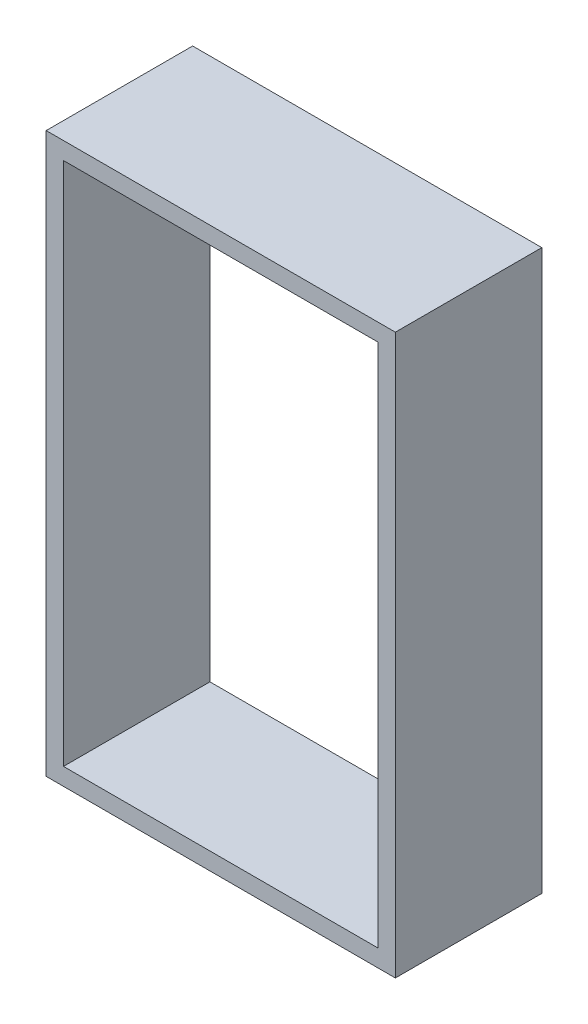
SolidWorks part; units mm, degrees
ref_plane "Front Plane" through (0, 0, 0) normal (0, 0, 1) x (1, 0, 0)
ref_plane "Top Plane" through (0, 0, 0) normal (0, 1, 0) x (1, 0, 0)
ref_plane "Right Plane" through (0, 0, 0) normal (1, 0, 0) x (0, 0, -1)
sketch "Strap Sketch" plane through (0, 0, 0) normal (0, 0, 1) x (1, 0, 0)
  line L0 (-25.55, -44.25) -> (4.73, -44.25)
  line L1 (4.73, -44.25) -> (4.73, 4.25)
  line L2 (4.73, 4.25) -> (-25.55, 4.25)
  line L3 (-25.55, 4.25) -> (-25.55, -44.25)
  line L4 (-24.05, -42.75) -> (3.23, -42.75)
  line L5 (3.23, -42.75) -> (3.23, 2.75)
  line L6 (3.23, 2.75) -> (-24.05, 2.75)
  line L7 (-24.05, 2.75) -> (-24.05, -42.75)
extrude "Strap" add sketch "Strap Sketch" along normal mid plane 12.7
ref_axis "Engine Axis" through (6.244, 0, 0) along (-1, 0, 0)
